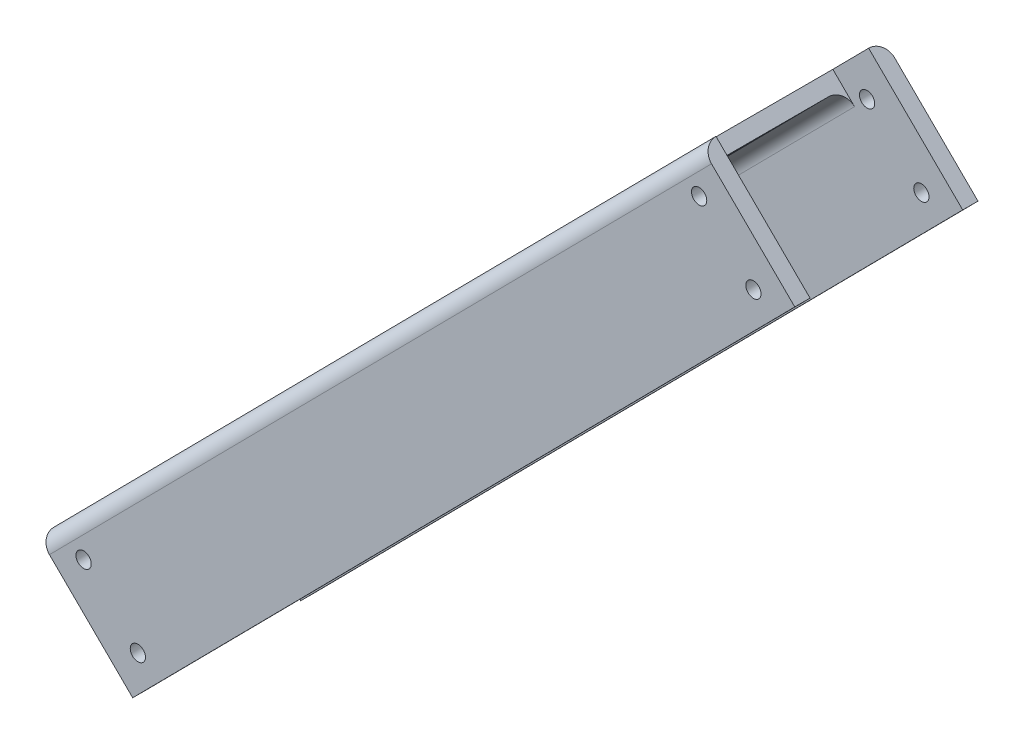
SolidWorks part; units mm, degrees
ref_plane "Front Plane" through (0, 0, 0) normal (0, 0, 1) x (1, 0, 0)
ref_plane "Top Plane" through (0, 0, 0) normal (0, 1, 0) x (1, 0, 0)
ref_plane "Right Plane" through (0, 0, 0) normal (1, 0, 0) x (0, 0, -1)
sketch "Sketch2" plane through (0, 0, 0) normal (0, 0, 1) x (1, 0, 0)
  line L0 (165.715, 148.457) -> (35.6364, 16.9102)
  line L1 (35.6364, 16.9102) -> (54.1241, -1.3711)
  line L4 (54.1241, -1.3711) -> (184.2027, 130.1757)
  line L25 (165.715, 148.457) -> (184.2027, 130.1757)
extrude "Boss-Extrude1" add sketch "Sketch2" against normal blind 3
sketch "Sketch4" plane through (0, 0, -36) normal (0, 0, -1) x (-1, 0, 0)
  line L6 (-165.715, 148.457) -> (-184.2027, 130.1757)
  line L9 (-184.2027, 130.1757) -> (-54.1241, -1.3711)
  line L10 (-54.1241, -1.3711) -> (-35.6364, 16.9102)
  line L11 (-35.6364, 16.9102) -> (-165.715, 148.457)
  line L12 (-165.715, 148.457) -> (-184.2027, 130.1757)
  line L15 (-184.2027, 130.1757) -> (-54.1241, -1.3711)
  line L16 (-54.1241, -1.3711) -> (-35.6364, 16.9102)
  line L17 (-35.6364, 16.9102) -> (-165.715, 148.457)
  dimension "D1" = 0
extrude "Boss-Extrude2" add sketch "Sketch4" against normal blind 3 separate body
sketch "Sketch5" plane through (0, 0, -3) normal (0, 0, -1) x (-1, 0, 0)
  line L0 (-35.6364, 16.9102) -> (-165.715, 148.457) construction
  line L1 (-35.6364, 16.9102) -> (-165.715, 148.457)
  line L2 (-37.7696, 14.8008) -> (-167.8482, 146.3476)
  line L3 (-37.7696, 14.8008) -> (-35.6364, 16.9102)
  line L4 (-167.8482, 146.3476) -> (-165.715, 148.457)
  dimension "D1" = 3
extrude "Boss-Extrude3" add sketch "Sketch5" along normal up to surface (30 mm away) up to face at (109.9195, 73.543, -33)
fillet "Fillet1" radius 3 4 edges at (102.8089, 80.5742, -3) (102.8089, 80.5742, -33) (100.6757, 82.6836, -36) (100.6757, 82.6836, 0)
sketch "Sketch6" plane through (9.5636, -9.4569, 0) normal (-0.7111, 0.7031, 0) x (0, 0, 1)
  circle A0 centre (-18, 197.0812) radius 7.5
extrude "Cut-Extrude1" cut sketch "Sketch6" against normal up to surface (3 mm away) up to face at (102.8089, 80.5742, -18)
sketch "Sketch7" plane through (9.5636, -9.4569, 0) normal (-0.7111, 0.7031, 0) x (0, 0, 1)
  line L5 (-3, 37.0812) -> (-3, 222.0812) construction
  line L6 (-3, 212.0812) -> (-3, 222.0812)
  line L7 (-33, 222.0812) -> (-33, 37.0812) construction
  line L8 (-33, 222.0812) -> (-33, 212.0812)
  line L9 (-33, 212.0812) -> (-3, 212.0812)
  line L12 (-33, 222.0812) -> (-3, 222.0812)
  line L13 (-36, 129.5812) -> (0, 129.5812) construction
  line L14 (-36, 37.0812) -> (-36, 222.0812) construction
  line L15 (0, 222.0812) -> (0, 37.0812) construction
  line L16 (-33, 37.0812) -> (-3, 37.0812)
  line L17 (-33, 47.0812) -> (-3, 47.0812)
  line L18 (-33, 37.0812) -> (-33, 47.0812)
  line L19 (-3, 47.0812) -> (-3, 37.0812)
extrude "Cut-Extrude2" cut sketch "Sketch7" against normal up to surface (26 mm away) up to face at (119.1634, 64.4023, -1.5)
sketch "Sketch8" plane through (0, 0, 0) normal (0, 0, 1) x (1, 0, 0)
  line L0 (58.6944, 3.2508) -> (40.2067, 21.5321) construction
  line L5 (179.6323, 125.5538) -> (161.1447, 143.8351) construction
  line L6 (158.6837, 141.3464) -> (165.715, 148.457) construction
  line L8 (100.6757, 82.6836) -> (119.1634, 64.4023) construction
  line L9 (42.6677, 24.0208) -> (158.6837, 141.3464) construction
  line L10 (54.1241, -1.3711) -> (184.2027, 130.1757) construction
  circle A0 centre (176.077, 129.0694) radius 1.5
  circle A1 centre (165.4111, 139.6163) radius 1.5
  circle A2 centre (44.4731, 17.3134) radius 1.5
  circle A3 centre (55.1391, 6.7664) radius 1.5
extrude "Cut-Extrude3" cut sketch "Sketch8" against normal up to surface (36 mm away) up to face at (110.9861, 72.4883, -36)
fillet "Fillet2" radius 1 2 edges at (142.8634, 125.3474, -18) (144.9966, 123.2381, -18)
